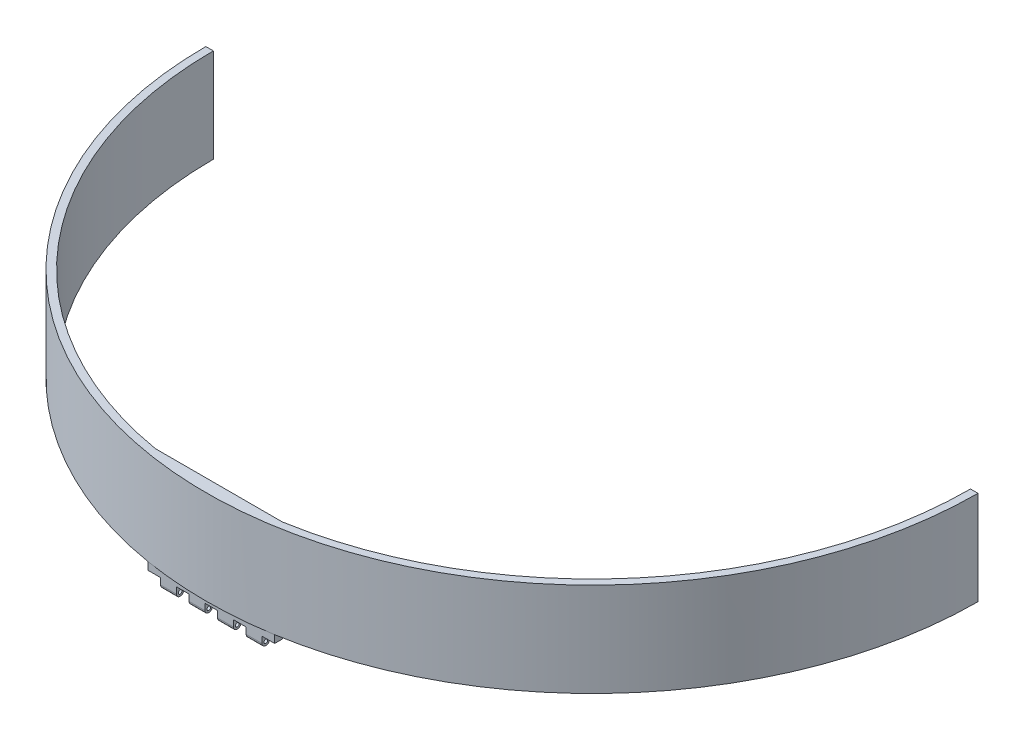
SolidWorks part; units mm, degrees
ref_plane "Front Plane" through (0, 0, 0) normal (0, 0, 1) x (1, 0, 0)
ref_plane "Top Plane" through (0, 0, 0) normal (0, 1, 0) x (1, 0, 0)
ref_plane "Right Plane" through (0, 0, 0) normal (1, 0, 0) x (0, 0, -1)
sketch "Sketch1" plane through (0, 0, 0) normal (0, 1, 0) x (1, 0, 0)
  line L1 (-25, 1.5) -> (25, 1.5)
  line L2 (-25, 1.5) -> (-25, -1.5)
  line L3 (-25, -1.5) -> (25, -1.5)
  line L4 (25, 1.5) -> (25, -1.5)
  line L5 (-25, 1.5) -> (25, -1.5) construction
  line L6 (-25, -1.5) -> (25, 1.5) construction
  point P0 (0, 0)
extrude "Boss-Extrude1" add sketch "Sketch1" along normal blind 40 contours L1 L4 L3 L2
sketch "Sketch2" plane through (0, 0, 0) normal (0, -1, 0) x (1, 0, 0)
  line L0 (-25, 1.5) -> (25, 1.5) construction
  line L1 (-20, 1.5) -> (-13.75, 1.5)
  line L2 (-20, 1.5) -> (-20, -1.5)
  line L3 (-20, -1.5) -> (-13.75, -1.5)
  line L4 (-13.75, 1.5) -> (-13.75, -1.5)
  line L5 (-16.875, -1.5) -> (-16.875, 1.5) construction
  line L6 (-20, 0) -> (-13.75, 0) construction
  line L7 (-25, -1.5) -> (25, -1.5) construction
  line L8 (-25, -1.5) -> (-25, 1.5) construction
  point P404 (-16.875, 0)
  dimension "D1" = 5
  dimension "D2" = 6.25
extrude "Boss-Extrude2" add sketch "Sketch2" along normal blind 4
fillet "Fillet1" radius 1.5 2 edges at (-16.875, -4, 1.5) (-16.875, -4, -1.5)
pattern_linear "LPattern1" count 4 spacing 11.25 along (1, 0, 0) of "Boss-Extrude2", "Fillet1"
sketch "Sketch3" plane through (25, 0, 0) normal (1, 0, 0) x (0, 0, -1)
  line L0 (1.5, 40) -> (1.5, 0) construction
  line L1 (-1.5, 40) -> (1.5, 40)
  line L2 (-1.5, 40) -> (-1.5, 3)
  line L3 (-1.5, 3) -> (1.5, 3)
  line L4 (1.5, 40) -> (1.5, 3)
  line L5 (0, 3) -> (0, 40) construction
  line L6 (-1.5, 21.5) -> (1.5, 21.5) construction
  point P664 (0, 21.5)
ref_plane "Plane1" through (0, 38.5, 0) normal (0, 1, 0) x (1, 0, 0)
sketch "Sketch7" plane through (0, 38.5, 0) normal (0, 1, 0) x (1, 0, 0)
  arc A0 (-149.86, 148.7751) -> (149.86, 148.7751) centre (0, 148.7751) ccw
  dimension "D1" = 0
  dimension "D2" = 149.86
  dimension "D3" = 0
sweep "Sweep2" add profiles "Sketch3" path "Sketch7"
sketch "Sketch8" plane through (-20, 0, 0) normal (-1, 0, 0) x (0, 0, 1)
  circle A0 centre (0, -2.5) radius 0.75
  arc A1 (-1.5, -2.5) -> (0, -4) centre (0, -2.5) ccw construction
  dimension "D1" = 0
extrude "Cut-Extrude1" cut sketch "Sketch8" against normal through all
sketch "Sketch9" plane through (0, 40, 0) normal (0, 1, 0) x (1, 0, 0)
  line L0 (-149.3819, 148.6943) -> (-152.3404, 148.6943)
  line L6 (152.3399, 148.3556) -> (149.3397, 148.3556)
  line L7 (149.3397, 148.3556) -> (149.3819, 148.856)
  line L8 (149.3819, 148.856) -> (152.3399, 148.3556)
  line L9 (-152.3404, 148.6943) -> (-152.4435, 148.6943)
  line L10 (-152.4435, 148.6943) -> (-152.4435, 149.268)
  line L11 (-152.4435, 149.268) -> (-149.3819, 148.6943)
  arc A0 (-152.3399, 149.1947) -> (152.3399, 148.3556) centre (0, 148.7751) ccw construction
extrude "Cut-Extrude2" cut sketch "Sketch9" against normal through all
